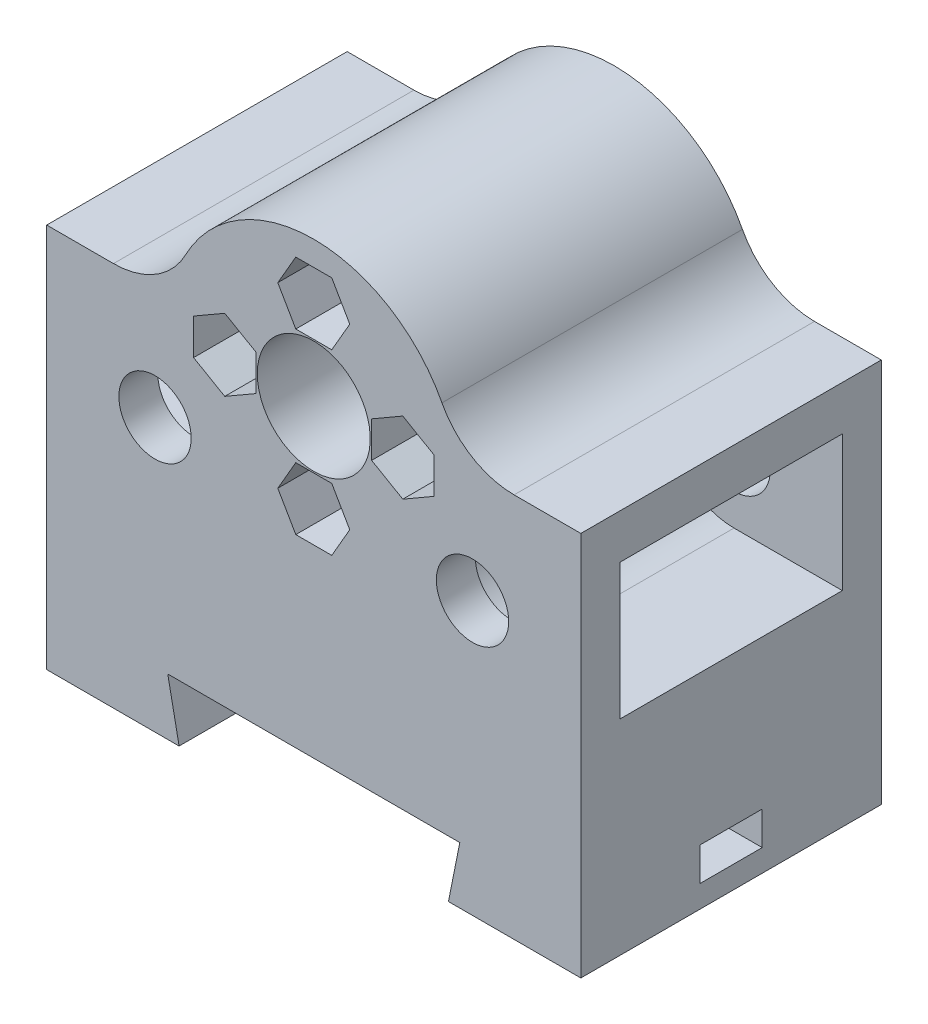
SolidWorks part; units mm, degrees
ref_plane "Front Plane" through (0, 0, 0) normal (0, 0, 1) x (1, 0, 0)
ref_plane "Top Plane" through (0, 0, 0) normal (0, 1, 0) x (1, 0, 0)
ref_plane "Right Plane" through (0, 0, 0) normal (1, 0, 0) x (0, 0, -1)
sketch "Sketch1" plane through (0, 0, 0) normal (0, 0, 1) x (1, 0, 0)
  line L1 (-24, -10) -> (24, -10)
  line L2 (-24, -10) -> (-24, 10)
  line L3 (-24, 10) -> (24, 10)
  line L4 (24, -10) -> (24, 10)
  line L5 (-24, -10) -> (24, 10) construction
  line L6 (-24, 10) -> (24, -10) construction
  line L7 (24, -10) -> (-24, -10)
  line L8 (24, -10) -> (24, -18)
  line L9 (24, -18) -> (-24, -18)
  line L10 (-24, -10) -> (-24, -18)
  circle A0 centre (0, 0) radius 13
  point P0 (0, 0)
  dimension "D3" = 26
  dimension "D1" = 48
  dimension "D2" = 20
  dimension "D4" = 8
extrude "Boss-Extrude1" add sketch "Sketch1" along normal mid plane 27 contours L3 A0 L1 | L3 A0 | A0 L1 L4 L3 | L1 A0 | A0 L3 L2 L1 | A0 L1 L10 L9 L8 | L7 A0 region at (-17.7116, 0, 0) region at (0, -14.2714, 0) region at (0, 0, 0) region at (0, -11.2127, 0) region at (17.7116, 0, 0) region at (0, 11.2127, 0)
sketch "Sketch2" plane through (0, 0, -13.5) normal (0, 0, -1) x (-1, 0, 0)
  circle A0 centre (0, 0) radius 5.075
  circle A1 centre (0, 0) radius 11.15
  dimension "D1" = 22.3
  dimension "D2" = 10.15
extrude "Cut-Extrude1" cut sketch "Sketch2" against normal blind 5 contours A0 | A1 A0 region at (0, 0, -13.5) region at (10.8346, 0, -13.5)
extrude "Cut-Extrude2" cut sketch "Sketch2<3>" against normal through all contours A0 region at (0, 0, -13.5)
sketch "Sketch2<3>" plane through (0, 0, -13.5) normal (0, 0, -1) x (-1, 0, 0) same geometry as "Sketch2"
sketch "Sketch3" plane through (0, 0, 0) normal (0, 0, 1) x (1, 0, 0)
  line L0 (-14.2661, -1.9) -> (-24, -1.9)
  line L1 (-24, -18) -> (-24, 10) construction
  line L2 (-24, -1.9) -> (-24, -14.1)
  line L3 (-24, -14.1) -> (-14.2661, -14.1)
  circle A0 centre (-14.2661, -8) radius 6.1
  dimension "D1" = 12.2
extrude "Cut-Extrude3" cut sketch "Sketch3" against normal mid plane 20 contours A0 | A0 L0 L2 L3 region at (-21.341, -8, 0) region at (-14.2661, -8, 0)
sketch "Sketch4" plane through (0, 0, -13.5) normal (0, 0, -1) x (-1, 0, 0)
  line L0 (24, -18) -> (24, 10) construction
  line L1 (24, 2.1) -> (31.3115, 2.1) construction
  line L2 (14.2661, -1.9) -> (24, -1.9) construction
  line L3 (24, 2.1) -> (18, 2.1)
  line L4 (24, 10) -> (8.3066, 10) construction
  line L5 (24, -18) -> (24, 10)
  line L6 (24, 10) -> (8.3066, 10)
  arc A0 (8.3066, 10) -> (11.5201, 6.024) centre (0, 0) cw
  arc A2 (18, 2.1) -> (11.5201, 6.024) centre (18, 9.4124) cw
  arc A3 (8.3066, 10) -> (-8.3066, 10) centre (0, 0) ccw construction
  circle A4 centre (0, 0) radius 11.15 construction
  line M7 (24, -18) -> (24, 10)
  line M8 (24, 10) -> (8.3066, 10)
  dimension "D2" = 6
  dimension "D1" = 4
extrude "Cut-Extrude4" cut sketch "Sketch4" against normal through all contours A2 L3 A0 M7 M8 region at (-17.7025, 6.4202, -13.5)
sketch "Sketch5" plane through (0, 0, 0) normal (0, 0, 1) x (1, 0, 0)
  circle A0 centre (-14.2661, -8) radius 3.25
  dimension "D1" = 6.5
extrude "Cut-Extrude5" cut sketch "Sketch5" against normal through all both and the other way through all
mirror "Mirror1" about plane through (0, 0, 0) normal (1, 0, 0) of "Cut-Extrude5", "Cut-Extrude4", "Cut-Extrude3"
hole_wizard "M3 Clearance Hole1" positions "Sketch6" profile "Sketch7" hole size "M3" standard "ISO" end condition through all
sketch "Sketch6" plane through (0, 0, -8.5) normal (0, 0, -1) x (-1, 0, 0)
  line L1 (0, 8) -> (-8, 0)
  line L2 (0, 8) -> (8, 0)
  line L3 (8, 0) -> (0, -8)
  line L4 (-8, 0) -> (0, -8)
  line L5 (0, 0) -> (0, 8) construction
  circle A0 centre (0, 0) radius 8 construction
  point P18 (-8, 0)
  point P20 (0, 8)
  point P22 (8, 0)
  point P24 (0, -8)
  dimension "D1" = 16
sketch "Sketch7" plane through (0, -8, -8.5) normal (1, 0, 0) x (0, 1, 0)
  line L0 (0, 0) -> (0, 22)
  line L1 (0, 22) -> (1.7, 22)
  line L2 (1.7, 22) -> (1.7, 0)
  line L5 (1.7, 0) -> (0, 0)
  line L11 (0, -6.35) -> (0, 107.95) construction
  dimension "Thru Hole Dia." = 3.4
  dimension "Thru Hole Depth" = 22
sketch "Sketch8" plane through (0, 0, 13.5) normal (0, 0, 1) x (1, 0, 0)
  line L0 (0, 0) -> (-8, 0) construction
  line L1 (-10.8, -1.6166) -> (-8, -3.2332)
  line L2 (-8, -3.2332) -> (-5.2, -1.6166)
  line L3 (-5.2, -1.6166) -> (-5.2, 1.6166)
  line L4 (-5.2, 1.6166) -> (-8, 3.2332)
  line L5 (-8, 3.2332) -> (-10.8, 1.6166)
  line L6 (-10.8, 1.6166) -> (-10.8, -1.6166)
  circle A0 centre (-8, 0) radius 2.8 construction
  dimension "D1" = 5.6
extrude "Cut-Extrude6" cut sketch "Sketch8" against normal blind 5
pattern_circular "CirPattern1" count 4 over 360 about axis through (0, 0, 13.5) along (0, 0, -1) of "Cut-Extrude6"
sketch "Sketch9" plane through (0, 0, 0) normal (0, 0, 1) x (1, 0, 0)
  line L0 (32.7589, -32.5) -> (-26.472, -32.5) construction
  line L1 (24, -18) -> (-24, -18) construction
  line L2 (12, -32.5) -> (13, -27.5)
  line L3 (24, -18) -> (-24, -18)
  line L4 (24, -18) -> (24, -32.5)
  line L5 (24, -32.5) -> (-24, -32.5)
  line L6 (-24, -18) -> (-24, -32.5)
  line L7 (13, -27.5) -> (-13, -27.5)
  line L8 (-13, -27.5) -> (-12, -32.5)
  point P15 (0, -27.5)
  point P16 (0, -32.5)
  dimension "D1" = 14.5
  dimension "D2" = 24
  dimension "D3" = 26
  dimension "D4" = 5
extrude "Boss-Extrude2" add sketch "Sketch9" along normal up to surface (13.5 mm away) and the other way up to surface (13.5 mm away) contours L8 L7 L2 L5 L4 L3 L6 region at (0, -24.2175, 0) up to face at (0, 8, 13.5) other way up to face at (11.0161, -8, -13.5)
hole_wizard "M3 Clearance Hole2" positions "Sketch10" profile "Sketch11" hole size "M3" standard "ISO"
sketch "Sketch10" plane through (0, -32.5, 0) normal (0, -1, 0) x (-1, 0, 0)
  line L0 (24, -13.5) -> (13, 13.5) construction
  line L1 (13, 13.5) -> (-13, 13.5) construction
  line L2 (13, -13.5) -> (13, 13.5) construction
  line L3 (-24, -13.5) -> (-13, 13.5) construction
  line L4 (-12, 13.5) -> (-24, 13.5) construction
  line L5 (-13, -13.5) -> (-13, 13.5) construction
  point P9 (18.5, 0)
  point P21 (-18.5, 0)
sketch "Sketch11" plane through (18.5, -32.5, 0) normal (1, 0, 0) x (0, 0, -1)
  line L0 (0, 0) -> (0, 13.0215)
  line L1 (0, 13.0215) -> (1.7, 12)
  line L2 (1.7, 12) -> (1.7, 0)
  line L5 (1.7, 0) -> (0, 0)
  line L10 (0, 13.0215) -> (-1.7, 12) construction
  line L11 (0, -6.35) -> (0, 107.95) construction
  dimension "Hole Dia." = 3.4
  dimension "Hole Depth" = 12
  dimension "Drill Angle" = 118
sketch "Sketch12" plane through (0, -32.5, 0) normal (0, -1, 0) x (1, 0, 0)
  line L0 (-20.1166, 2.8) -> (-24, 2.8)
  line L1 (-20.1166, 2.8) -> (-21.7332, 0)
  line L2 (-21.7332, 0) -> (-20.1166, -2.8)
  line L3 (-20.1166, -2.8) -> (-16.8834, -2.8)
  line L4 (-16.8834, -2.8) -> (-15.2668, 0)
  line L5 (-15.2668, 0) -> (-16.8834, 2.8)
  line L6 (-16.8834, 2.8) -> (-20.1166, 2.8)
  line L7 (20.1166, 2.8) -> (16.8834, 2.8)
  line L8 (16.8834, 2.8) -> (15.2668, 0)
  line L9 (15.2668, 0) -> (16.8834, -2.8)
  line L10 (16.8834, -2.8) -> (20.1166, -2.8)
  line L11 (20.1166, -2.8) -> (21.7332, 0)
  line L12 (21.7332, 0) -> (20.1166, 2.8)
  line L13 (-24, 13.5) -> (-24, -13.5) construction
  line L14 (-24, 2.8) -> (-24, -2.8)
  line L15 (-24, -2.8) -> (-20.1166, -2.8)
  line L16 (20.1166, 2.8) -> (24, 2.8)
  line L17 (24, 13.5) -> (24, -13.5) construction
  line L18 (24, 2.8) -> (24, -2.8)
  line L19 (24, -2.8) -> (20.1166, -2.8)
  circle A0 centre (-18.5, 0) radius 2.8 construction
  circle A1 centre (18.5, 0) radius 2.8 construction
  circle M4 centre (-18.5, 0) radius 1.7
  line M7 (-24, 13.5) -> (-24, -13.5)
  dimension "D1" = 5.6
extrude "Cut-Extrude7" cut sketch "Sketch12" against normal blind 3 from offset 2 contours L11 L12 L7 L8 L9 L10 | L19 L18 L16 L12 L11 | L5 L6 L1 L2 L3 L4 M4 | L15 L2 L1 L0 M7 region at (-22.427, -32.5, 0) region at (-18.5, -32.5, 2.7145) region at (18.5, -32.5, 0) region at (22.427, -32.5, 0) offset against normal yes
sketch "Sketch13" plane through (0, 0, 13.5) normal (0, 0, 1) x (1, 0, 0)
  line L3 (-12.0981, -32.5196) -> (12.0981, -32.5196)
  line L6 (12.0981, -32.5196) -> (13.122, -27.4)
  line L7 (13.122, -27.4) -> (-13.122, -27.4)
  line L8 (-13.122, -27.4) -> (-12.0981, -32.5196)
  line L9 (12.0981, -32.5196) -> (13.122, -27.4)
  line L10 (13.122, -27.4) -> (-13.122, -27.4)
  line L11 (-13.122, -27.4) -> (-12.0981, -32.5196)
  dimension "D1" = 0.1
extrude "Cut-Extrude8" cut sketch "Sketch13" against normal through all
